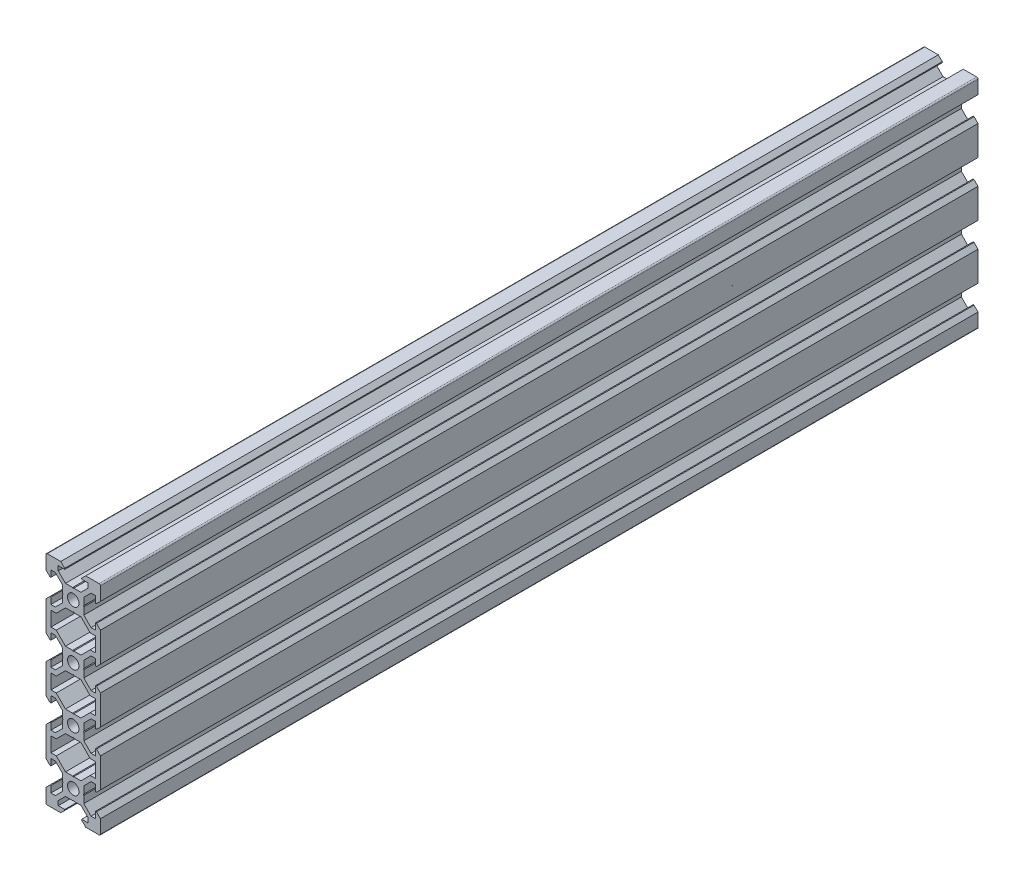
SolidWorks part; units mm, degrees
ref_plane "Plan de face" through (0, 0, 0) normal (0, 0, 1) x (1, 0, 0)
ref_plane "Plan de dessus" through (0, 0, 0) normal (0, 1, 0) x (1, 0, 0)
ref_plane "Plan de droite" through (0, 0, 0) normal (1, 0, 0) x (0, 0, -1)
ref_axis "Axe" through (0, 0, -13.782) along (0, 0, 1)
sketch "Esquisse1" plane through (0, 0, 0) normal (0, 0, 1) x (1, 0, 0)
  line L0 (0, 27.6392) -> (0, -27.6392) construction
  line L1 (-33.6074, 0) -> (33.6074, 0) construction
  line L2 (0, 0) -> (-22.2114, 22.2114) construction
  line L3 (-9.5, 10) -> (-4.58, 10)
  line L4 (-4.58, 10) -> (-3.125, 8.545)
  line L5 (-3.125, 8.545) -> (-3.125, 8.2)
  line L6 (-3.125, 8.2) -> (-5.5, 8.2)
  line L7 (-2.8393, 3.9) -> (-5.5, 6.5607)
  line L8 (-2.8393, 3.9) -> (-0.21, 3.9)
  line L9 (-5.5, 6.5607) -> (-5.5, 8.2)
  line L10 (0, 3.69) -> (0, 2.1)
  line L11 (-3.9, 2.8393) -> (-6.5607, 5.5)
  line L12 (-8.545, 3.125) -> (-8.2, 3.125)
  line L13 (-8.2, 3.125) -> (-8.2, 5.5)
  line L14 (-6.5607, 5.5) -> (-8.2, 5.5)
  line L15 (-10, 4.58) -> (-8.545, 3.125)
  line L16 (-10, 9.5) -> (-10, 4.58)
  line L17 (-0.21, 3.9) -> (0, 3.69)
  line L18 (-3.9, 2.8393) -> (-3.9, 0.21)
  line L19 (-6.2393, -12.7) -> (-8.2, -12.7)
  line L20 (-3.9, 0.21) -> (-3.69, 0)
  line L21 (-0.21, -3.9) -> (0, -3.69)
  line L22 (0, -3.69) -> (0, -2.1)
  line L23 (-6.5607, -5.5) -> (-8.2, -5.5)
  line L24 (-2.8393, -3.9) -> (-0.21, -3.9)
  line L25 (-8.545, -3.125) -> (-8.2, -3.125)
  line L26 (-10, -4.58) -> (-8.545, -3.125)
  line L27 (-8.2, -3.125) -> (-8.2, -5.5)
  line L28 (-2.8393, -3.9) -> (-6.2393, -7.3)
  line L29 (-3.9, -2.8393) -> (-6.5607, -5.5)
  line L30 (-3.9, -2.8393) -> (-3.9, -0.21)
  line L31 (-3.9, -0.21) -> (-3.69, 0)
  line L32 (-6.2393, -7.3) -> (-8.2, -7.3)
  line L33 (-8.2, -7.3) -> (-8.2, -12.7)
  line L34 (-8.2, -10) -> (-10, -10) construction
  line L35 (-10, -15.42) -> (-10, -4.58)
  line L36 (-3.9, -19.79) -> (-3.69, -20)
  line L37 (-3.9, -17.1607) -> (-3.9, -19.79)
  line L38 (-3.9, -17.1607) -> (-6.5607, -14.5)
  line L39 (-2.8393, -16.1) -> (-6.2393, -12.7)
  line L40 (-8.2, -16.875) -> (-8.2, -14.5)
  line L41 (-10, -15.42) -> (-8.545, -16.875)
  line L42 (-8.545, -16.875) -> (-8.2, -16.875)
  line L43 (-2.8393, -16.1) -> (-0.21, -16.1)
  line L44 (-6.5607, -14.5) -> (-8.2, -14.5)
  line L45 (0, -16.31) -> (0, -17.9)
  line L46 (-0.21, -16.1) -> (0, -16.31)
  line L47 (-8.2, -30) -> (-10, -30) construction
  line L48 (-3.69, -20) -> (0, -20) construction
  line L49 (-0.21, -23.9) -> (0, -23.69)
  line L50 (0, -23.69) -> (0, -22.1)
  line L51 (-6.5607, -25.5) -> (-8.2, -25.5)
  line L52 (-2.8393, -23.9) -> (-0.21, -23.9)
  line L53 (-8.545, -23.125) -> (-8.2, -23.125)
  line L54 (-10, -24.58) -> (-8.545, -23.125)
  line L55 (-8.2, -23.125) -> (-8.2, -25.5)
  line L56 (-2.8393, -23.9) -> (-6.2393, -27.3)
  line L57 (-3.9, -22.8393) -> (-6.5607, -25.5)
  line L58 (-3.9, -22.8393) -> (-3.9, -20.21)
  line L59 (-3.9, -20.21) -> (-3.69, -20)
  line L60 (-10, -24.58) -> (-10, -35.42)
  line L61 (-8.2, -32.7) -> (-8.2, -27.3)
  line L62 (-3.69, -40) -> (0, -40) construction
  line L63 (-8.2, -50) -> (-10, -50) construction
  line L64 (0, -60) -> (-22.2114, -82.2114) construction
  line L65 (-33.6074, -60) -> (33.6074, -60) construction
  line L66 (0, -87.6392) -> (0, -32.3608) construction
  line L67 (-6.2393, -32.7) -> (-8.2, -32.7)
  line L68 (-3.9, -39.79) -> (-3.69, -40)
  line L69 (-3.9, -37.1607) -> (-3.9, -39.79)
  line L70 (-3.9, -37.1607) -> (-6.5607, -34.5)
  line L71 (-2.8393, -36.1) -> (-6.2393, -32.7)
  line L72 (-8.2, -36.875) -> (-8.2, -34.5)
  line L73 (-10, -35.42) -> (-8.545, -36.875)
  line L74 (-8.545, -36.875) -> (-8.2, -36.875)
  line L75 (-6.2393, -27.3) -> (-8.2, -27.3)
  line L76 (-2.8393, -36.1) -> (-0.21, -36.1)
  line L77 (-6.5607, -34.5) -> (-8.2, -34.5)
  line L78 (0, -36.31) -> (0, -37.9)
  line L79 (-0.21, -36.1) -> (0, -36.31)
  line L80 (-0.21, -43.9) -> (0, -43.69)
  line L81 (0, -43.69) -> (0, -42.1)
  line L82 (-6.5607, -45.5) -> (-8.2, -45.5)
  line L83 (-2.8393, -43.9) -> (-0.21, -43.9)
  line L84 (-8.545, -43.125) -> (-8.2, -43.125)
  line L85 (-10, -44.58) -> (-8.545, -43.125)
  line L86 (-8.2, -43.125) -> (-8.2, -45.5)
  line L87 (-2.8393, -43.9) -> (-6.2393, -47.3)
  line L88 (-3.9, -42.8393) -> (-6.5607, -45.5)
  line L89 (-3.9, -42.8393) -> (-3.9, -40.21)
  line L90 (-3.9, -40.21) -> (-3.69, -40)
  line L91 (-10, -44.58) -> (-10, -55.42)
  line L92 (-8.2, -52.7) -> (-8.2, -47.3)
  line L93 (-6.2393, -52.7) -> (-8.2, -52.7)
  line L94 (-3.9, -59.79) -> (-3.69, -60)
  line L95 (-3.9, -57.1607) -> (-3.9, -59.79)
  line L96 (-3.9, -57.1607) -> (-6.5607, -54.5)
  line L97 (-2.8393, -56.1) -> (-6.2393, -52.7)
  line L98 (-8.2, -56.875) -> (-8.2, -54.5)
  line L99 (-10, -55.42) -> (-8.545, -56.875)
  line L100 (-8.545, -56.875) -> (-8.2, -56.875)
  line L101 (-2.8393, -56.1) -> (-0.21, -56.1)
  line L102 (-6.5607, -54.5) -> (-8.2, -54.5)
  line L103 (0, -56.31) -> (0, -57.9)
  line L104 (-0.21, -56.1) -> (0, -56.31)
  line L105 (-3.9, -60.21) -> (-3.69, -60)
  line L106 (-6.2393, -47.3) -> (-8.2, -47.3)
  line L107 (-3.9, -62.8393) -> (-3.9, -60.21)
  line L108 (-0.21, -63.9) -> (0, -63.69)
  line L109 (-10, -69.5) -> (-10, -64.58)
  line L110 (-10, -64.58) -> (-8.545, -63.125)
  line L111 (-6.5607, -65.5) -> (-8.2, -65.5)
  line L112 (-8.2, -63.125) -> (-8.2, -65.5)
  line L113 (-8.545, -63.125) -> (-8.2, -63.125)
  line L114 (-3.9, -62.8393) -> (-6.5607, -65.5)
  line L115 (0, -63.69) -> (0, -62.1)
  line L116 (-5.5, -66.5607) -> (-5.5, -68.2)
  line L117 (-2.8393, -63.9) -> (-0.21, -63.9)
  line L118 (-2.8393, -63.9) -> (-5.5, -66.5607)
  line L119 (-3.125, -68.2) -> (-5.5, -68.2)
  line L120 (-3.125, -68.545) -> (-3.125, -68.2)
  line L121 (-4.58, -70) -> (-3.125, -68.545)
  line L122 (-9.5, -70) -> (-4.58, -70)
  arc A0 (0, -2.1) -> (0, 2.1) centre (0, 0) cw
  arc A1 (-9.5, 10) -> (-10, 9.5) centre (-9.5, 9.5) ccw
  arc A2 (0, -42.1) -> (0, -37.9) centre (0, -40) cw
  arc A3 (-9.5, -70) -> (-10, -69.5) centre (-9.5, -69.5) cw
  arc A4 (0, -17.9) -> (0, -22.1) centre (0, -20) ccw
  arc A5 (0, -57.9) -> (0, -62.1) centre (0, -60) ccw
  point P4 (0, 0)
  point P7 (0, 0)
  point P30 (-10, 10)
  point P60 (0, -20)
  point P146 (-10, -70)
  dimension "D5" = 11
  dimension "D2" = 2.1
  dimension "D3" = 6.25
  dimension "D10" = 0.5
  dimension "D4" = 9.16
  dimension "D6" = 1.5
  dimension "D7" = 1.8
  dimension "D8" = 4.3
  dimension "D9" = 20
  dimension "D11" = 0.42
  dimension "D12" = 10
  dimension "D13" = 1.8
extrude "Boss.-Extru.1" add sketch "Esquisse1" along normal blind 322.5
sketch "Esquisse3" plane through (0, 0, 322.5) normal (0, 0, 1) x (1, 0, 0)
  line L0 (0, 0) -> (-9.8536, 9.8536) construction
  line L1 (-8.2, 8.2) -> (-8.2, 6.57)
  line L2 (-8.2, 6.57) -> (-7.54, 6.57)
  line L3 (-7.54, 6.57) -> (-6.57, 7.54)
  line L4 (-8.2, 3.125) -> (-8.2, 5.5) construction
  line L5 (-6.57, 8.2) -> (-6.57, 7.54)
  line L6 (-8.2, 8.2) -> (-6.57, 8.2)
  line L7 (-5.5, 6.5607) -> (-5.5, 8.2) construction
  line L8 (-10, -30) -> (6.918, -30) construction
  line L9 (-10, -24.58) -> (-10, -35.42) construction
  line L10 (-8.2, -68.2) -> (-6.57, -68.2)
  line L11 (-6.57, -68.2) -> (-6.57, -67.54)
  line L12 (-7.54, -66.57) -> (-6.57, -67.54)
  line L13 (-8.2, -66.57) -> (-7.54, -66.57)
  line L14 (-8.2, -68.2) -> (-8.2, -66.57)
  arc A0 (-9.5, 10) -> (-10, 9.5) centre (-9.5, 9.5) ccw construction
  point P13 (-7.055, 7.055)
  point P14 (-6.57, 7.87)
  point P26 (-7.055, -67.055)
  dimension "D1" = 1.07
extrude "Enlèv. mat.-Extru.1" [suppressed] cut sketch "Esquisse3" against normal through all
mirror "Symétrie1" about plane through (0, 3.69, 322.5) normal (-1, 0, 0) of "Enlèv. mat.-Extru.1", "Boss.-Extru.1"
